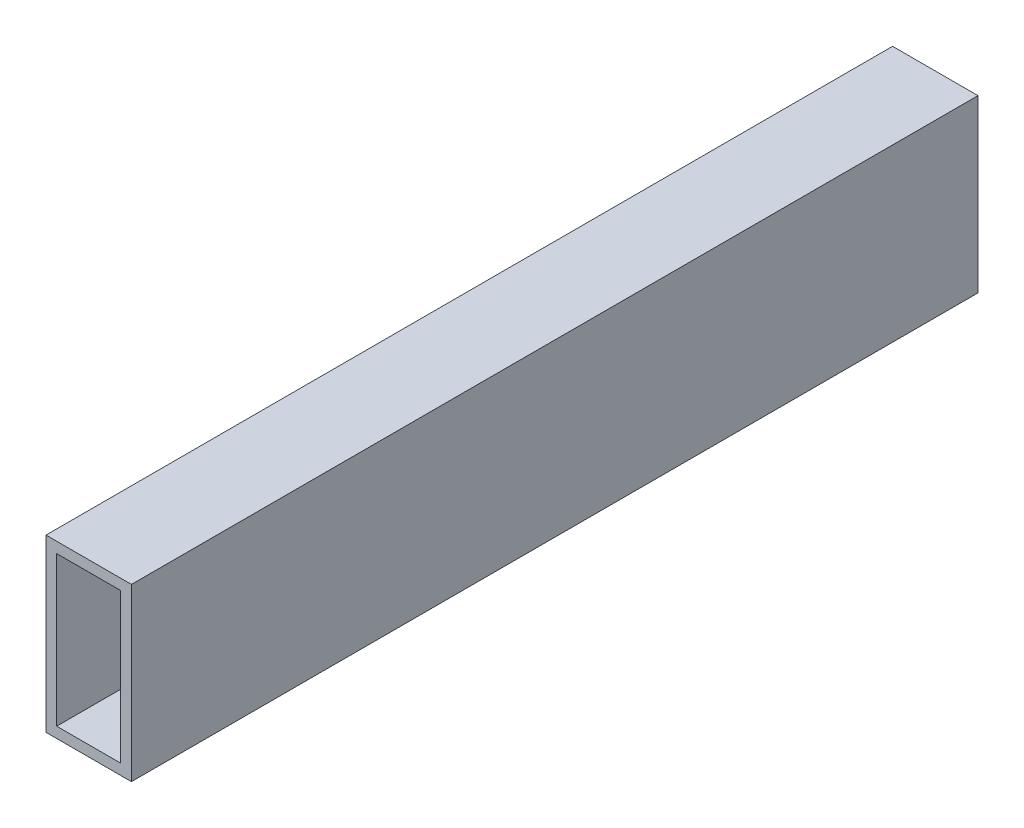
SolidWorks part; units mm, degrees
material "6061 Alloy"
ref_plane "Front Plane" through (0, 0, 0) normal (0, 0, 1) x (1, 0, 0)
ref_plane "Top Plane" through (0, 0, 0) normal (0, 1, 0) x (1, 0, 0)
ref_plane "Right Plane" through (0, 0, 0) normal (1, 0, 0) x (0, 0, -1)
sketch "Sketch1" plane through (0, 0, 0) normal (0, 0, 1) x (1, 0, 0)
  line L0 (0, 25.4) -> (0, 22.225) construction
  line L1 (-12.7, 25.4) -> (12.7, 25.4)
  line L2 (-12.7, 25.4) -> (-12.7, -25.4)
  line L3 (-12.7, -25.4) -> (12.7, -25.4)
  line L4 (12.7, 25.4) -> (12.7, -25.4)
  line L5 (-12.7, 25.4) -> (12.7, -25.4) construction
  line L6 (-12.7, -25.4) -> (12.7, 25.4) construction
  line L7 (-9.525, 22.225) -> (9.525, 22.225)
  line L8 (-9.525, 22.225) -> (-9.525, -22.225)
  line L9 (-9.525, -22.225) -> (9.525, -22.225)
  line L10 (9.525, 22.225) -> (9.525, -22.225)
  line L11 (9.525, 0) -> (12.7, 0) construction
  line L12 (-9.525, 0) -> (-12.7, 0) construction
  line L13 (0, -22.225) -> (0, -25.4) construction
  point P0 (0, 0)
  dimension "D1" = 50.8
  dimension "D2" = 25.4
  dimension "D3" = 3.175
extrude "Boss-Extrude1" add sketch "Sketch1" along normal blind 251.714
